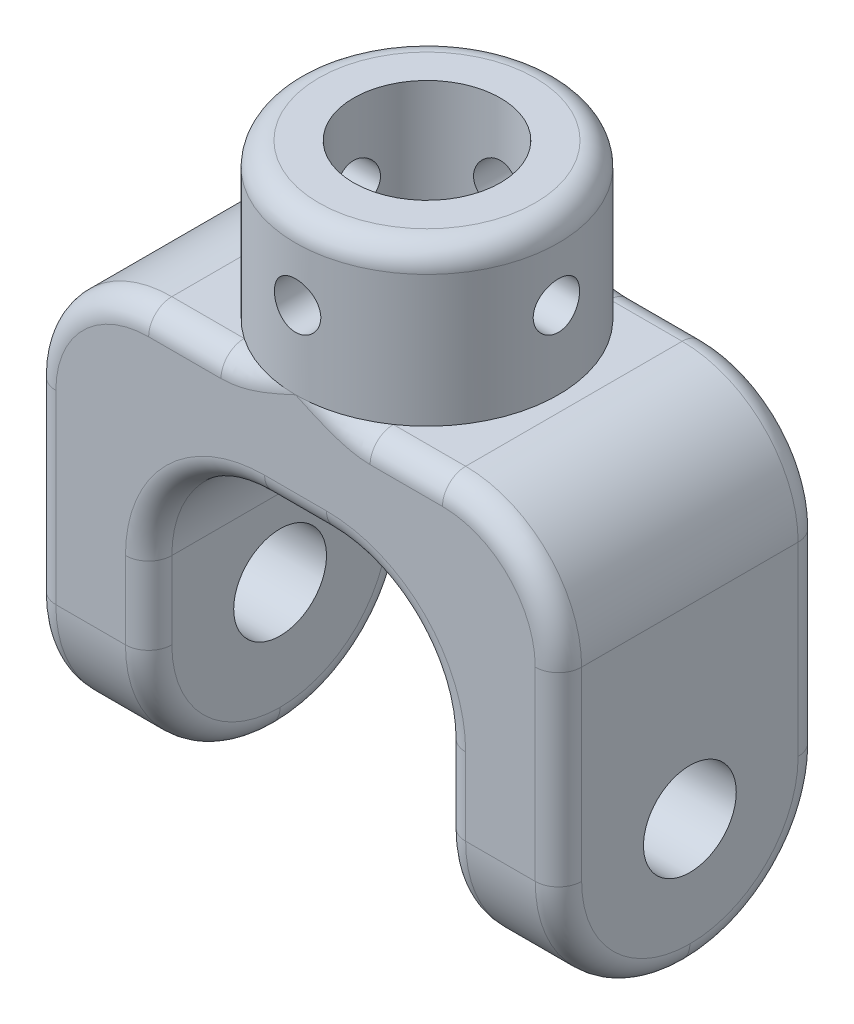
SolidWorks part; units mm, degrees
material "Gray Cast Iron"
ref_plane "Front Plane" through (0, 0, 0) normal (0, 0, 1) x (1, 0, 0)
ref_plane "Top Plane" through (0, 0, 0) normal (0, 1, 0) x (1, 0, 0)
ref_plane "Right Plane" through (0, 0, 0) normal (1, 0, 0) x (0, 0, -1)
sketch "Sketch1" plane through (0, 0, 0) normal (0, 0, 1) x (1, 0, 0)
  line L0 (56, 0) -> (65, 0)
  line L1 (3, 0) -> (12, 0)
  line L2 (0, 3) -> (0, 41)
  line L3 (15, 56) -> (53, 56)
  line L4 (68, 3) -> (68, 41)
  line L6 (15, 3) -> (15, 27)
  line L7 (30, 42) -> (38, 42)
  line L8 (53, 3) -> (53, 27)
  arc A0 (68, 41) -> (53, 56) centre (53, 41) ccw
  arc A1 (15, 56) -> (0, 41) centre (15, 41) ccw
  arc A2 (68, 3) -> (65, 0) centre (65, 3) cw
  arc A3 (0, 3) -> (3, 0) centre (3, 3) ccw
  arc A4 (53, 27) -> (38, 42) centre (38, 27) ccw
  arc A5 (30, 42) -> (15, 27) centre (30, 27) ccw
  arc A6 (53, 3) -> (56, 0) centre (56, 3) ccw
  arc A7 (12, 0) -> (15, 3) centre (12, 3) ccw
  point P7 (68, 56)
  point P12 (68, 0)
  point P15 (0, 0)
  point P22 (53, 42)
  point P27 (53, 0)
  point P30 (15, 0)
  dimension "D3" = 15
  dimension "D4" = 3
  dimension "D8" = 15
  dimension "D9" = 3
  dimension "D1" = 68
  dimension "D2" = 56
  dimension "D5" = 15
  dimension "D6" = 15
  dimension "D7" = 42
extrude "Boss-Extrude2" add sketch "Sketch1" along normal blind 34 contours L2 A1 L3 A0 L4 A2 L0 A6 L8 A4 L7 A5 L6 A7 L1 A3
sketch "Sketch3" plane through (0, 56, 0) normal (0, 1, 0) x (1, 0, 0)
  line L0 (0, -34) -> (0, 0) construction
  line L1 (15, 0) -> (53, 0) construction
  circle A0 centre (34, -17) radius 17
  dimension "D1" = 34
  dimension "D3" = 34
  dimension "D4" = 17
extrude "Boss-Extrude3" add sketch "Sketch3" along normal blind 20
sketch "Sketch4" plane through (0, 76, 0) normal (0, 1, 0) x (1, 0, 0)
  line L0 (15, 0) -> (34, 0) construction
  line L1 (0, -34) -> (0, 0) construction
  circle A0 centre (34, -17) radius 9.5
  dimension "D1" = 19
  dimension "D2" = 17
  dimension "D3" = 34
extrude "Cut-Extrude1" cut sketch "Sketch4" against normal blind 44
sketch "Sketch5" plane through (68, 0, 0) normal (1, 0, 0) x (0, 0, -1)
  line L0 (-34, 3) -> (-34, 41) construction
  line L1 (-34, 0) -> (0, 0) construction
  line L2 (0, 17) -> (0, 0)
  line L3 (0, 0) -> (-34, 0)
  line L4 (-34, 0) -> (-34, 17)
  circle A0 centre (-17, 17) radius 6
  arc A1 (-34, 17) -> (0, 17) centre (-17, 17) ccw
  line M2 (0, 3) -> (0, 41)
  line M4 (-34, 41) -> (-34, 3)
  line M5 (-34, 3) -> (0, 3)
  dimension "D1" = 12
  dimension "D2" = 17
  dimension "D3" = 17
extrude "Cut-Extrude2" cut sketch "Sketch5" against normal blind 84 contours A1 M5 M2 | A1 L3 L2 M5 | A1 L4 L3 M5 | A1 M4 M5 | A0 region at (68, 6.3307, 2.0913) region at (68, 1.3179, 5.4668) region at (68, 1.3179, 28.5332) region at (68, 6.3307, 31.9087) region at (68, 17, 17)
sketch "Sketch6" plane through (68, 0, 0) normal (1, 0, 0) x (0, 0, -1)
  line L0 (0, 56) -> (0, 76) construction
  line L1 (-7.5, 76) -> (-26.5, 76) construction
  circle A0 centre (-17, 66) radius 3
  dimension "D1" = 6
  dimension "D2" = 17
  dimension "D3" = 10
extrude "Cut-Extrude3" cut sketch "Sketch6" against normal blind 84
sketch "Sketch7" plane through (0, 0, 34) normal (0, 0, 1) x (1, 0, 0)
  line L0 (51, 76) -> (17, 76) construction
  line L1 (51, 56) -> (51, 63.0001) construction
  circle A0 centre (34, 66) radius 3
  dimension "D1" = 6
  dimension "D2" = 10
  dimension "D3" = 17
extrude "Cut-Extrude4" cut sketch "Sketch7" against normal blind 84
fillet "Fillet1" radius 3 31 edges at (34, 76, 34) (24.5, 56, 0) (53, 9.0925, 1.951) (53, 22, 0) (34, 42, 0) (48.6066, 37.6066, 0) (19.3934, 37.6066, 0) (15, 22, 0) (15, 9.0925, 1.951) (19.3934, 37.6066, 34) (15, 22, 34) (15, 9.0925, 32.049) (53, 9.0925, 32.049) (53, 22, 34) (48.6066, 37.6066, 34) (34, 42, 34) (68, 9.0925, 1.951) (68, 29, 0) (43.5, 56, 0) (63.6066, 51.6066, 0) (43.5, 56, 34) (24.5, 56, 34) (68, 9.0925, 32.049) (68, 29, 34) (63.6066, 51.6066, 34) (4.3934, 51.6066, 0) (0, 29, 0) (0, 9.0925, 1.951) (0, 9.0925, 32.049) (0, 29, 34) (4.3934, 51.6066, 34)
